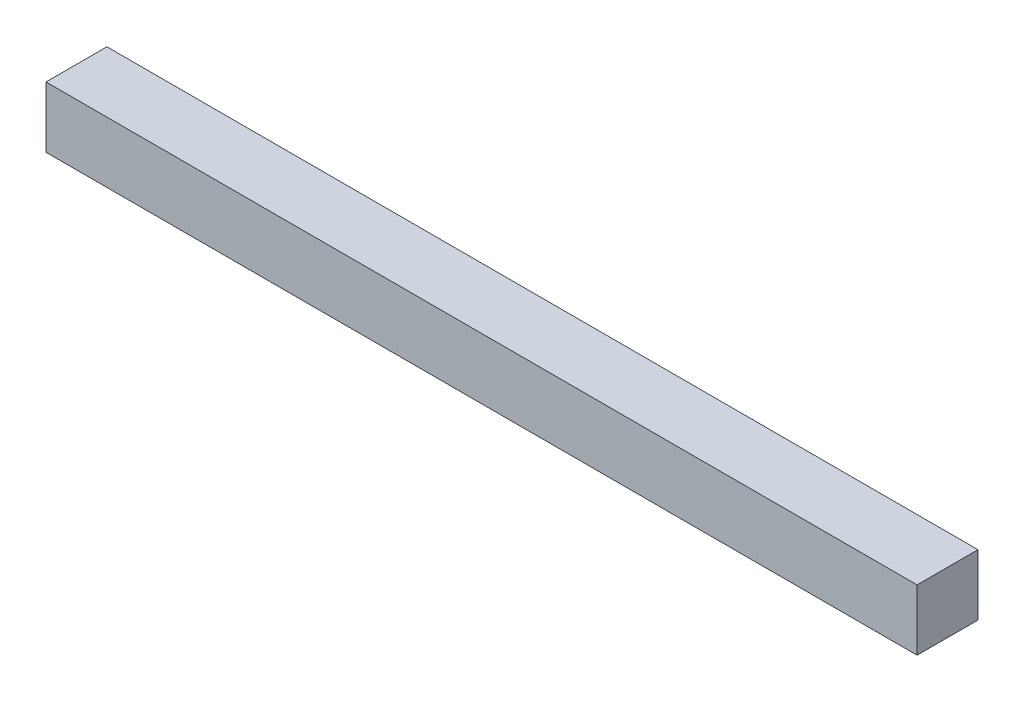
SolidWorks part; units mm, degrees
ref_plane "Plan de face" through (0, 0, 0) normal (0, 0, 1) x (1, 0, 0)
ref_plane "Plan de dessus" through (0, 0, 0) normal (0, 1, 0) x (1, 0, 0)
ref_plane "Plan de droite" through (0, 0, 0) normal (1, 0, 0) x (0, 0, -1)
sketch "Esquisse1" plane through (0, 0, 0) normal (0, 0, 1) x (1, 0, 0)
  line L1 (-5.3833, 3.1991) -> (137.6167, 3.1991)
  line L2 (-5.3833, 3.1991) -> (-5.3833, -6.8009)
  line L3 (-5.3833, -6.8009) -> (137.6167, -6.8009)
  line L4 (137.6167, 3.1991) -> (137.6167, -6.8009)
  dimension "D1" = 143
  dimension "D2" = 10
extrude "Boss.-Extru.1" add sketch "Esquisse1" along normal blind 10 contours L3 L4 L1 L2
equation "\"mm\"=10"
equation "\"D1@Esquisse1\"=\"LargeurBoite\" - \"LargeurGauche\" + 13"
equation "\"EpaisseurPlaque\"= 3"
equation "\"ProfondeurBoite\"=460"
equation "\"LongueurSyphon\"=170"
equation "\"LargeurSyphon\"=120"
equation "\"HauteurCoteDroit\"= 490"
equation "\"HauteurCoteGauche\"= 540"
equation "\"HauteurSolSyphon\"= 300"
equation "\"HauteurSyphon\"=\"HauteurCoteGauche\"-\"HauteurSolSyphon\""
equation "\"LargeurDroite\"=10"
equation "\"LargeurGauche\"=150"
equation "\"LargeurBoite\"= \"LargeurDroite\" + \"LargeurGauche\" + \"LargeurSyphon\""
